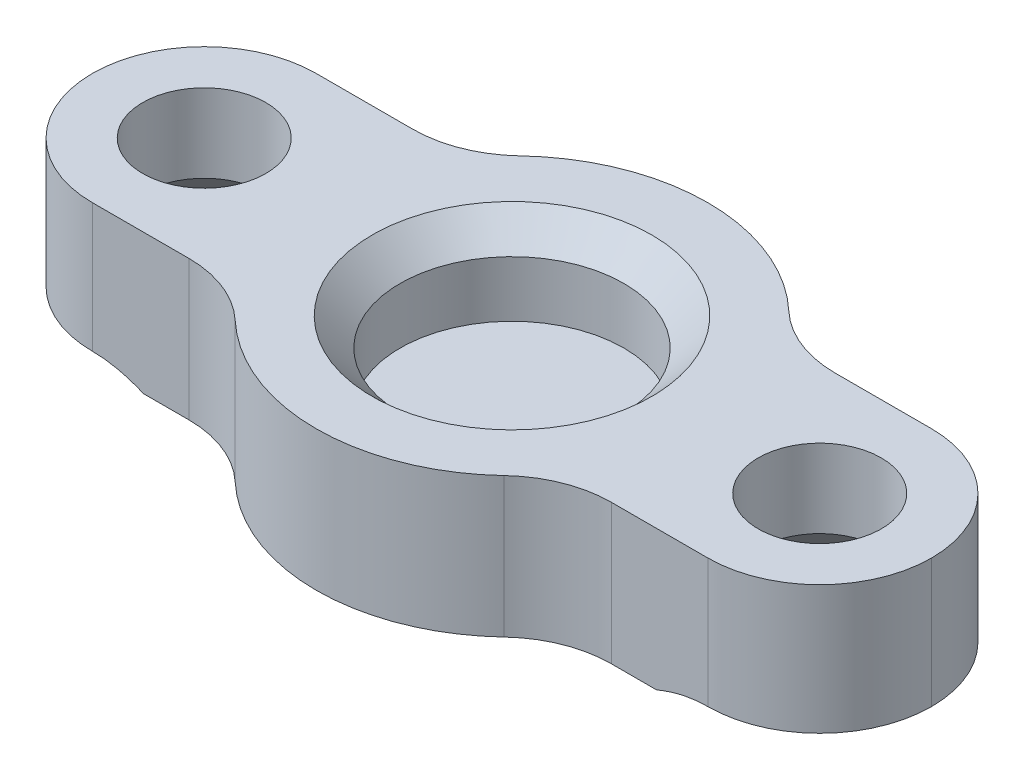
SolidWorks part; units mm, degrees
ref_plane "Front Plane" through (0, 0, 0) normal (0, 0, 1) x (1, 0, 0)
ref_plane "Top Plane" through (0, 0, 0) normal (0, 1, 0) x (1, 0, 0)
ref_plane "Right Plane" through (0, 0, 0) normal (1, 0, 0) x (0, 0, -1)
sketch "Sketch1" plane through (0, 0, 0) normal (0, 0, 1) x (1, 0, 0)
  line L0 (0, 0) -> (0, 7.0462) construction
  line L1 (0, 0) -> (-3.5, 0)
  line L2 (-3.5, 0) -> (-3.5, 2.5)
  line L3 (-3.5, 2.5) -> (-2, 2.5)
  line L4 (-2, 2.5) -> (-2, 1)
  line L5 (-2, 1) -> (0, 1)
  line L6 (0, 0) -> (0, 1)
  point P3 (-8.7639, 13.1346)
  point P9 (-2, 3.3122)
  point P10 (-4.98, 5.9228)
  point P11 (-4.6989, 0)
  point P12 (-2, 1.5878)
  point P13 (-3.8489, 3.0506)
  point P14 (0, 7.0462)
  dimension "D1" = 2
  dimension "D2" = 1.5
  dimension "D3" = 1
  dimension "D4" = 1.5
revolve "Revolve1" add sketch "Sketch1" angle 360 about L0
chamfer "Chamfer2" distance 0.5 angle 45 1 edges at (0, 2.5, -2)
sketch "Sketch2" plane through (0, 2.5, 0) normal (0, 1, 0) x (1, 0, 0)
  line L0 (-2.8723, -2) -> (-7.5, -2)
  line L1 (-7.5, -2) -> (-7.5, 2)
  line L2 (-7.5, 2) -> (-2.8723, 2)
  line L3 (-7.5, 0) -> (-3.5, 0) construction
  line L4 (-2.8723, -2) -> (-2.8723, 2)
  circle A0 centre (0, 0) radius 3.5 construction
  point P2 (-7.5, 0)
  dimension "D1" = 4
extrude "Boss-Extrude1" add sketch "Sketch2" against normal up to surface (2.5 mm away) up to face at (0, 0, -3.5)
fillet "Fillet1" radius 2 4 edges at (-2.8723, 1.25, 2) (-2.8723, 1.25, -2) (-7.5, 1.25, -2) (-7.5, 1.25, 2)
hole_wizard "CSK for M2 Flat Head Machine Screw1" positions "Sketch3" profile "Sketch4" countersink size "M2" standard "ANSI Metric"
sketch "Sketch3" plane through (0, 0, 0) normal (0, -1, 0) x (-1, 0, 0)
  arc A1 (7.5, 0) -> (5.5, 2) centre (5.5, 0) ccw construction
  point P0 (5.5, 0)
  point P6 (0, 0)
sketch "Sketch4" plane through (-5.5, 0, 0) normal (1, 0, 0) x (0, 0, -1)
  line L0 (0, 0) -> (0, 5.8609)
  line L1 (0, 5.8609) -> (1.1, 5.2)
  line L2 (1.1, 5.2) -> (1.1, 1.1)
  line L3 (1.1, 1.1) -> (2.2, 0)
  line L5 (2.2, 0) -> (0, 0)
  line L6 (-1.1, 1.1) -> (-2.2, 0) construction
  line L10 (0, 5.8609) -> (-1.1, 5.2) construction
  line L11 (0, -6.35) -> (0, 107.95) construction
  dimension "Hole Dia." = 2.2
  dimension "Hole Depth" = 5.2
  dimension "Near C'Sink Dia." = 4.4
  dimension "Near C'Sink Angle" = 90
  dimension "Drill Angle" = 118
pattern_circular "CirPattern1" count 2 over 360 about axis through (0, 0, 0) along (0, -1, 0) of "CSK for M2 Flat Head Machine Screw1", "Boss-Extrude1", "Fillet1"
